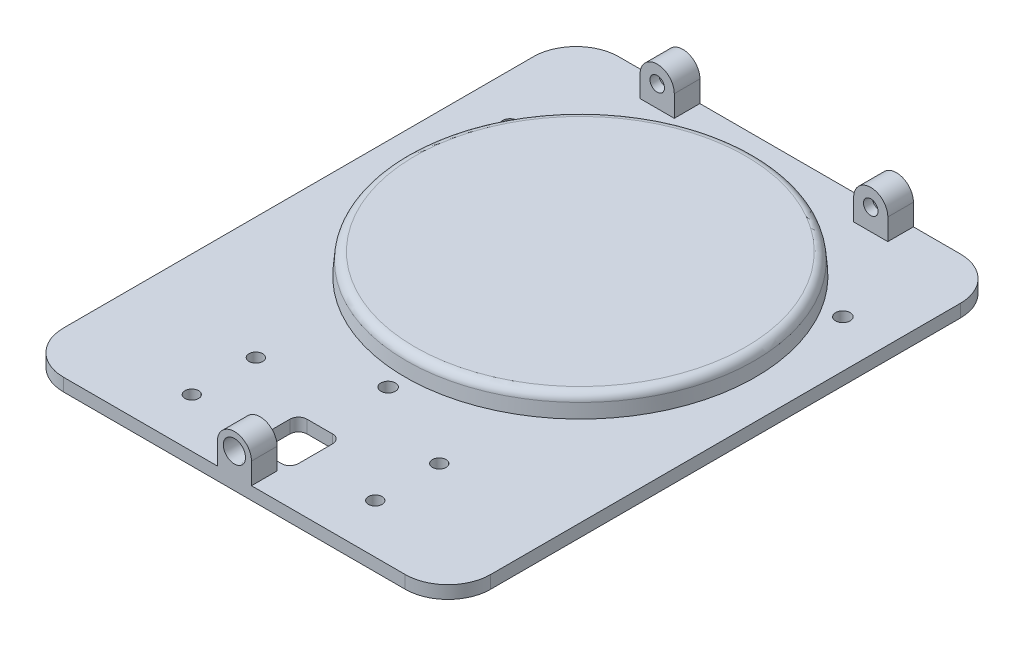
SolidWorks part; units mm, degrees
ref_plane "Front" through (0, 0, 0) normal (0, 0, 1) x (1, 0, 0)
ref_plane "Top" through (0, 0, 0) normal (0, 1, 0) x (1, 0, 0)
ref_plane "Right" through (0, 0, 0) normal (1, 0, 0) x (0, 0, -1)
sketch "Sketch1" plane through (0, 0, 0) normal (0, 1, 0) x (1, 0, 0)
  line L1 (0, 65) -> (0, -65) construction
  line L3 (40, -65) -> (-40, -65)
  line L4 (50, -55) -> (50, 55)
  line L5 (40, 65) -> (-40, 65)
  line L6 (-50, -55) -> (-50, 55)
  line L7 (50, -65) -> (-50, 65) construction
  line L8 (50, 65) -> (-50, -65) construction
  line L9 (3, -57) -> (-3, -57)
  line L10 (5, -55) -> (5, -47)
  line L11 (3, -45) -> (-3, -45)
  line L12 (-5, -55) -> (-5, -47)
  line L13 (5, -57) -> (-5, -45) construction
  line L14 (5, -45) -> (-5, -57) construction
  arc A0 (-50, 55) -> (-40, 65) centre (-40, 55) cw
  arc A1 (40, 65) -> (50, 55) centre (40, 55) cw
  arc A2 (50, -55) -> (40, -65) centre (40, -55) cw
  arc A3 (-40, -65) -> (-50, -55) centre (-40, -55) cw
  circle A8 centre (21.475, -38.5) radius 1.6
  circle A9 centre (21.475, -53.5) radius 1.6
  circle A10 centre (-21.475, -38.5) radius 1.6
  circle A11 centre (-21.475, -53.5) radius 1.6
  circle A13 centre (0, 16) radius 42.5 construction
  circle A14 centre (0, -29) radius 1.7
  circle A15 centre (-38.9711, 38.5) radius 1.7
  circle A16 centre (38.9711, 38.5) radius 1.7
  arc A17 (3, -57) -> (5, -55) centre (3, -55) ccw
  arc A18 (5, -47) -> (3, -45) centre (3, -47) ccw
  arc A19 (-3, -45) -> (-5, -47) centre (-3, -47) ccw
  arc A20 (-5, -55) -> (-3, -57) centre (-3, -55) ccw
  point P2 (0, 0)
  point P8 (0, -51)
  point P44 (0, 16)
  dimension "D2" = 10
  dimension "D3" = 3.4
  dimension "D9" = 2
  dimension "D1" = 100
  dimension "D4" = 45
  dimension "D6" = 12
  dimension "D7" = 10
  dimension "D8" = 8
  dimension "D5" = 3
extrude "Boss-Extrude1" add sketch "Sketch1" against normal blind 3
sketch "Sketch2" plane through (0, 0, 0) normal (0, 1, 0) x (1, 0, 0)
  circle A2 centre (0, 16) radius 41
  circle A3 centre (0, 16) radius 41
  dimension "D1" = 0.5
extrude "Boss-Extrude2" add sketch "Sketch2" along normal blind 5 draft 5
fillet "Fillet1" radius 2 1 edges at (0, 5, 24.5626)
sketch "Sketch3" plane through (0, 0, 0) normal (0, 0, 1) x (1, 0, 0)
  line L0 (-40, 0) -> (40, 0) construction
  line L1 (-40, 0) -> (40, 0) construction
  line L2 (-4, 5) -> (-4, 0)
  line L3 (4, 5) -> (4, 0)
  line L4 (-4, 0) -> (4, 0)
  line L5 (21, 5) -> (21, 0)
  line L6 (21, 0) -> (29, 0)
  line L7 (29, 5) -> (29, 0)
  line L8 (0, -50) -> (0, 50) construction
  line L9 (-29, 5) -> (-29, 0)
  line L10 (-21, 0) -> (-29, 0)
  line L11 (-21, 5) -> (-21, 0)
  circle A0 centre (0, 5) radius 1.7
  circle A1 centre (0, 5) radius 2.6
  arc A2 (4, 5) -> (-4, 5) centre (0, 5) ccw
  arc A3 (29, 5) -> (21, 5) centre (25, 5) ccw
  circle A4 centre (25, 5) radius 2.6
  circle A5 centre (25, 5) radius 1.7
  arc A6 (-29, 5) -> (-21, 5) centre (-25, 5) cw
  circle A7 centre (-25, 5) radius 2.6
  circle A8 centre (-25, 5) radius 1.7
  point P10 (0, 0)
  dimension "D1" = 3.4
  dimension "D2" = 5.2
  dimension "D3" = 4
  dimension "D4" = 5
  dimension "D6" = 25
  dimension "D5" = 2
extrude "Boss-Extrude3" add sketch "Sketch3" against normal blind 6 from surface contours L3 A2 L2 L4 A1 | A1 A0 region at (0, 8.8796, 0) region at (-2.5265, 5, 0) starting at face at (0, -1.5, 65)
extrude "Boss-Extrude4" add sketch "Sketch3<3>" along normal blind 6 from surface contours A6 L9 L10 L11 A7 | L7 A3 L5 L6 A4 | A4 A5 | A7 A8 region at (25, 8.8796, 0) region at (-25, 8.8796, 0) region at (22.4735, 5, 0) region at (-27.5265, 5, 0) starting at face at (0, -1.5, -65)
sketch "Sketch3<3>" plane through (0, 0, 0) normal (0, 0, 1) x (1, 0, 0) same geometry as "Sketch3"
extrude "Cut-Extrude1" cut sketch "Sketch3<4>" against normal blind 3.9 draft 1.5 from surface contours A1 starting at face at (0, 1, 65)
sketch "Sketch3<4>" plane through (0, 0, 0) normal (0, 0, 1) x (1, 0, 0) same geometry as "Sketch3"
extrude "Cut-Extrude2" cut sketch "Sketch3<5>" along normal blind 3.9 draft 1.5 from surface contours A4 | A7 starting at face at (0, 1.8333, -65)
sketch "Sketch3<5>" plane through (0, 0, 0) normal (0, 0, 1) x (1, 0, 0) same geometry as "Sketch3"
